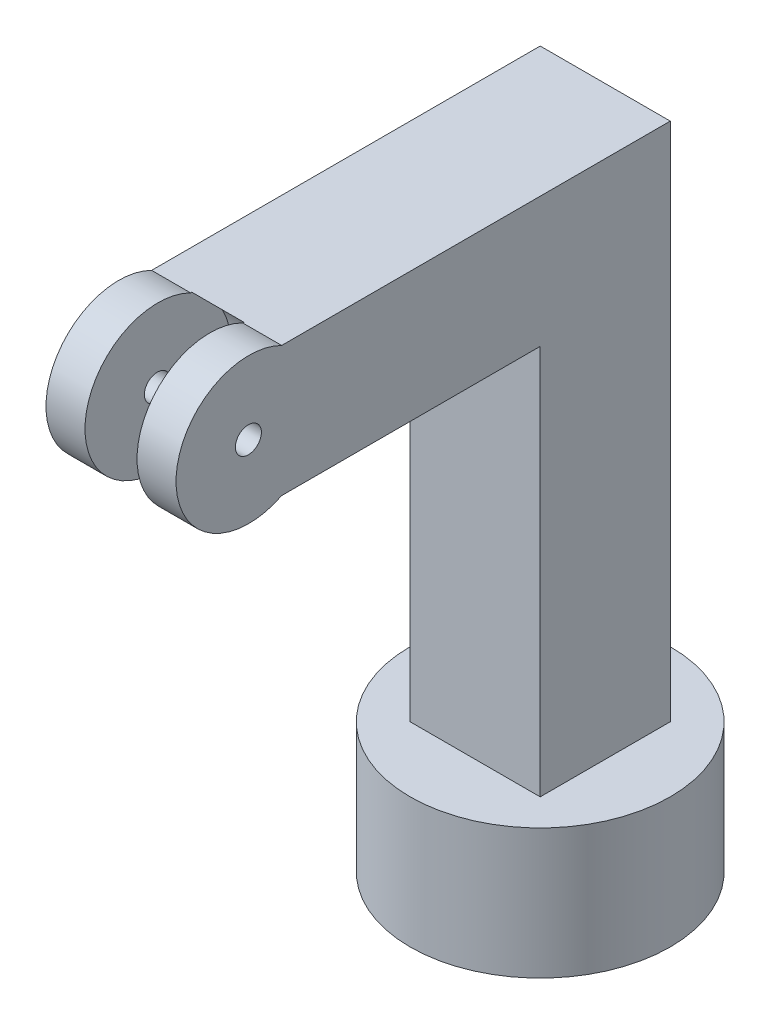
SolidWorks part; units mm, degrees
ref_plane "Front Plane" through (0, 0, 0) normal (0, 0, 1) x (1, 0, 0)
ref_plane "Top Plane" through (0, 0, 0) normal (0, 1, 0) x (1, 0, 0)
ref_plane "Right Plane" through (0, 0, 0) normal (1, 0, 0) x (0, 0, -1)
sketch "Sketch1" plane through (0, 0, 0) normal (0, 1, 0) x (1, 0, 0)
  circle A0 centre (0, 0) radius 25
  dimension "D1" = 50
extrude "Boss-Extrude1" add sketch "Sketch1" along normal blind 25
sketch "Sketch2" plane through (0, 25, 0) normal (0, 1, 0) x (1, 0, 0)
  line L1 (12.5, 12.5) -> (-12.5, 12.5)
  line L2 (12.5, 12.5) -> (12.5, -12.5)
  line L3 (12.5, -12.5) -> (-12.5, -12.5)
  line L4 (-12.5, 12.5) -> (-12.5, -12.5)
  line L5 (12.5, 12.5) -> (-12.5, -12.5) construction
  line L6 (12.5, -12.5) -> (-12.5, 12.5) construction
  point P0 (0, 0)
  dimension "D1" = 25
  dimension "D2" = 25
extrude "Boss-Extrude2" add sketch "Sketch2" along normal blind 100
sketch "Sketch7" plane through (0, 0, 0) normal (0, -1, 0) x (1, 0, 0)
  circle A0 centre (0, 0) radius 5
  dimension "D1" = 10
extrude "Cut-Extrude2" cut sketch "Sketch7" against normal blind 10
ref_axis "Axis7" through (0, -25.9913, 0) along (0, 1, 0)
sketch "Sketch8" plane through (0, 0, 12.5) normal (0, 0, 1) x (1, 0, 0)
  line L0 (12.5, 125) -> (12.5, 25) construction
  line L1 (-12.5, 125) -> (12.5, 125)
  line L2 (-12.5, 125) -> (-12.5, 100)
  line L3 (-12.5, 100) -> (12.5, 100)
  line L4 (12.5, 125) -> (12.5, 100)
  dimension "D1" = 25
extrude "Boss-Extrude3" add sketch "Sketch8" along normal blind 50
sketch "Sketch10" plane through (0, 0, 0) normal (1, 0, 0) x (0, 0, -1)
  line L0 (-62.5, 100) -> (-62.5, 125) construction
  circle A1 centre (-68.5, 112.5) radius 14
  dimension "D1" = 28
  dimension "D2" = 6
extrude "Boss-Extrude4" add sketch "Sketch10" along normal mid plane 25
sketch "Sketch13" plane through (0, 0, 0) normal (1, 0, 0) x (0, 0, -1)
  line L0 (0, -7.3003) -> (0, 147.7628) construction
  line L1 (21.0476, 112.5) -> (-89.54, 112.5) construction
  line L2 (-62.1952, 125) -> (12.5, 125) construction
  line L3 (-62.1952, 125) -> (-62.1952, 100) construction
  circle A0 centre (-68.5952, 112.5) radius 14.15
  dimension "D2" = 28.3
  dimension "D1" = 12.5
  dimension "D3" = 6.4
extrude "Cut-Extrude4" cut sketch "Sketch13" against normal mid plane 10
sketch "Sketch14" plane through (0, 0, 0) normal (1, 0, 0) x (0, 0, -1)
  line L0 (0, -8.8469) -> (0, 144.4251) construction
  line L1 (24.8154, 112.5) -> (-117.8362, 112.5) construction
  line L2 (-62.1952, 125) -> (12.5, 125) construction
  line L3 (-62.1952, 125) -> (-62.1952, 100) construction
  circle A0 centre (-68.5952, 112.5) radius 2.5
  dimension "D2" = 5
  dimension "D1" = 12.5
  dimension "D3" = 6.4
extrude "Cut-Extrude5" cut sketch "Sketch14" against normal through all both and the other way through all
ref_axis "Axis8" through (-25.6291, 112.5, 68.5952) along (1, 0, 0)
ref_plane "Plane4" through (0, 112.5, 0) normal (0, 1, 0) x (1, 0, 0)
ref_axis "Axis10" through (0, 112.5, -30.375) along (0, 0, 1)
ref_point "Point1"
ref_point "Point2"
ref_axis "Axis11" through (0, 10, 0) along (0, -1, 0)
